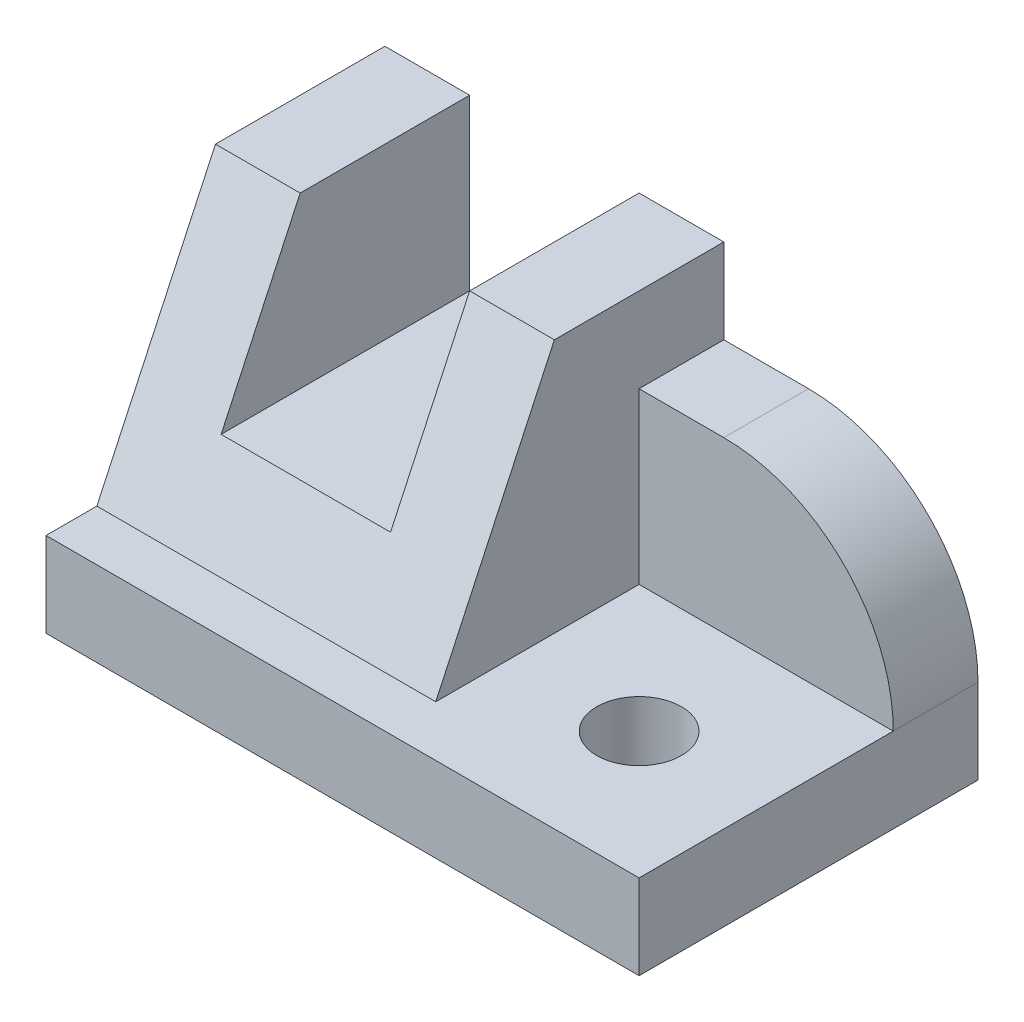
SolidWorks part; units mm, degrees
ref_plane "Front Plane" through (0, 0, 0) normal (0, 0, 1) x (1, 0, 0)
ref_plane "Top Plane" through (0, 0, 0) normal (0, 1, 0) x (1, 0, 0)
ref_plane "Right Plane" through (0, 0, 0) normal (1, 0, 0) x (0, 0, -1)
ref_plane "Plane1" through (0, 0, 0) normal (-1, 0, 0) x (0, -1, 0)
sketch "Sketch1" plane through (0, 0, 0) normal (-1, 0, 0) x (0, -1, 0)
  line L0 (-10, -6) -> (-40, -20)
  line L1 (-40, -20) -> (-10, -20)
  line L2 (-10, -20) -> (-10, -6)
  dimension "D1" = 30
  dimension "Width" = 14
extrude "Boss-Extrude1" add sketch "Sketch1" against normal blind 40
sketch "Sketch2" plane through (0, 0, -20) normal (0, 0, -1) x (-1, 0, 0)
  line L0 (-40, 40) -> (0, 40)
  line L1 (0, 40) -> (0, 10)
  line L2 (0, 10) -> (-40, 10)
  line L3 (-40, 10) -> (-40, 40)
extrude "Boss-Extrude2" add sketch "Sketch2" along normal blind 20
sketch "Sketch3" plane through (40, 0, 0) normal (1, 0, 0) x (0, 0, -1)
  line L0 (40, 10) -> (0, 10)
  line L1 (0, 10) -> (20, 40)
  line L2 (20, 40) -> (40, 40)
  line L3 (40, 40) -> (40, 10)
extrude "Boss-Extrude3" add sketch "Sketch3" along normal blind 30
sketch "Sketch4" plane through (70, 0, 0) normal (1, 0, 0) x (0, 0, -1)
  line L0 (20, 40) -> (0, 10)
  line L1 (0, 10) -> (30, 10)
  line L2 (30, 10) -> (30, 30)
  line L3 (30, 30) -> (40, 30)
  line L4 (40, 30) -> (40, 40)
  line L5 (40, 40) -> (20, 40)
extrude "Cut-Extrude1" cut sketch "Sketch4" against normal blind 30
sketch "Sketch5" plane through (0, 10, 0) normal (0, -1, 0) x (1, 0, 0)
  line L0 (70, 0) -> (70, -40)
  line L1 (70, -40) -> (0, -40)
  line L2 (0, -40) -> (0, 0)
  line L3 (0, 0) -> (70, 0)
extrude "Boss-Extrude4" add sketch "Sketch5" along normal blind 10
sketch "Sketch6" plane through (0, 0, -40) normal (0, 0, -1) x (-1, 0, 0)
  line L0 (-30, 40) -> (-30, 20)
  line L1 (-30, 20) -> (-10, 20)
  line L2 (-10, 20) -> (-10, 40)
  line L3 (-10, 40) -> (-30, 40)
extrude "Cut-Extrude2" cut sketch "Sketch6" against normal through all
hole_wizard "Ø10.0 (10) Diameter Hole1" positions "Sketch8" profile "Sketch7" hole size "Ø10.0" standard "ANSI Metric"
sketch "Sketch8" plane through (0, 0, 0) normal (0, -1, 0) x (-1, 0, 0)
  point P0 (-55, 15)
sketch "Sketch7" plane through (55, 0, -15) normal (1, 0, 0) x (0, 0, -1)
  line L0 (0, 0) -> (0, 40)
  line L1 (0, 40) -> (5, 40)
  line L2 (5, 40) -> (5, 0)
  line L5 (5, 0) -> (0, 0)
  line L11 (0, -6.35) -> (0, 107.95) construction
  dimension "Thru Hole Dia." = 10
  dimension "Thru Hole Depth" = 40
fillet "Fillet1" radius 20 1 edges at (70, 30, -35) tangent propagation no
